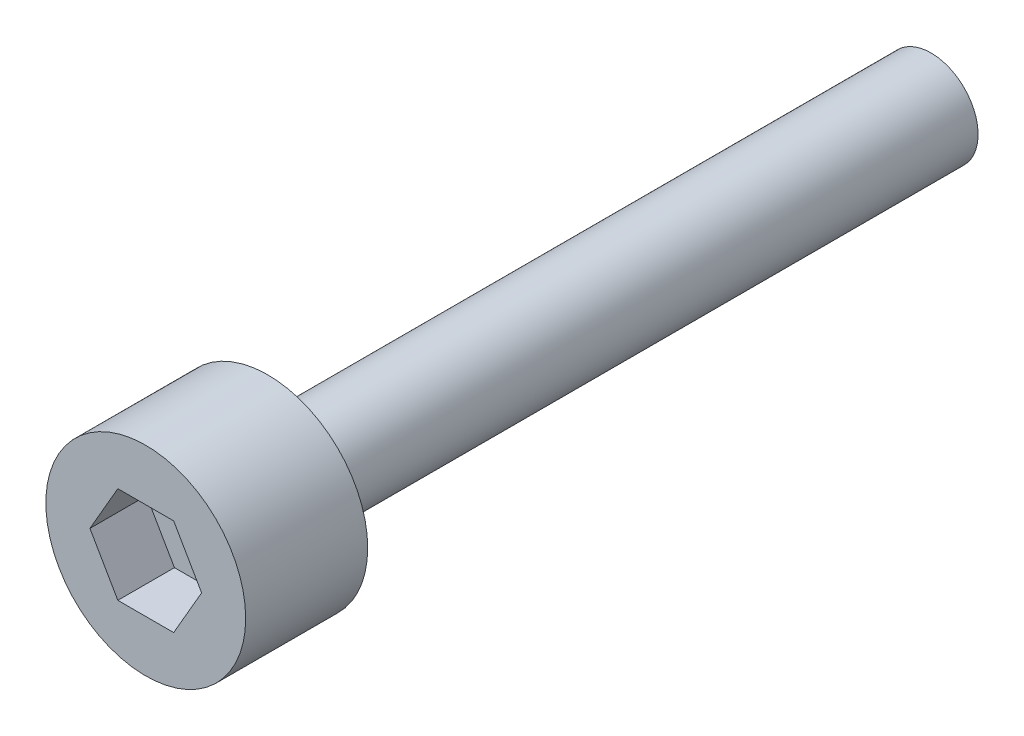
SolidWorks part; units mm, degrees
material "Alloy Steel"
ref_plane "Plane1" through (0, 0, 0) normal (0, 0, 1) x (1, 0, 0)
ref_plane "Plane2" through (0, 0, 0) normal (0, 1, 0) x (1, 0, 0)
ref_plane "Plane3" through (0, 0, 0) normal (1, 0, 0) x (0, 0, -1)
ref_axis "Axis1" through (-83.9706, 0, 0) along (1, 0, 0)
ref_axis "Axis2" through (0, 0, -20.1778) along (0, 0, 1)
ref_axis "Axis3" through (0, 3.1572, 0) along (0, -1, 0)
sketch "Sketch1" plane through (0, 0, 0) normal (0, 0, 1) x (1, 0, 0)
  circle A0 centre (0, 0) radius 2.8702
  dimension "D1" = 5.7404
extrude "Boss-Extrude1" add sketch "Sketch1" along normal blind 3.5052
sketch "Sketch2" plane through (0, 0, 0) normal (0, 0, -1) x (-1, 0, 0)
  circle A0 centre (0, 0) radius 1.7526
  dimension "D1" = 3.5052
extrude "Boss-Extrude2" add sketch "Sketch2" along normal blind 19.05
sketch "Sketch3" plane through (0, 0, -19.05) normal (0, 0, -1) x (-1, 0, 0)
  circle A0 centre (0, 0) radius 1.3525
  dimension "D1" = 2.7051
extrude "Cut-Extrude1" cut sketch "Sketch3" against normal blind 19.05 flip side to cut
sketch "Sketch4" plane through (0, 0, 3.5052) normal (0, 0, 1) x (1, 0, 0)
  line L1 (0.802, 1.3891) -> (-0.802, 1.3891)
  line L2 (-0.802, 1.3891) -> (-1.604, 0)
  line L3 (-1.604, 0) -> (-0.802, -1.3891)
  line L4 (-0.802, -1.3891) -> (0.802, -1.3891)
  line L5 (0.802, -1.3891) -> (1.604, 0)
  line L6 (1.604, 0) -> (0.802, 1.3891)
  circle A0 centre (0, 0) radius 1.3891 construction
  dimension "D1" = 2.7781
extrude "Cut-Extrude2" cut sketch "Sketch4" against normal blind 1.6256
equation "\"hd_wid\"= 0.226"
equation "\"hd_ht\"= 0.138"
equation "\"shank\"= 0.138"
equation "\"tap\"= 0.1065"
equation "\"length\"= 0.75"
equation "\"drive_size\"= 0.109375"
equation "\"drive_dep\"= 0.064"
equation "\"D1@Sketch1\" = \"hd_wid\""
equation "\"D1@Boss-Extrude1\" = \"hd_ht\""
equation "\"D1@Sketch2\" = \"shank\""
equation "\"D1@Boss-Extrude2\" = \"length\""
equation "\"D1@Sketch3\" = \"tap\""
equation "\"D1@Cut-Extrude1\" = \"length\""
equation "\"D1@Sketch4\" = \"drive_size\""
equation "\"D1@Cut-Extrude2\" = \"drive_dep\""
